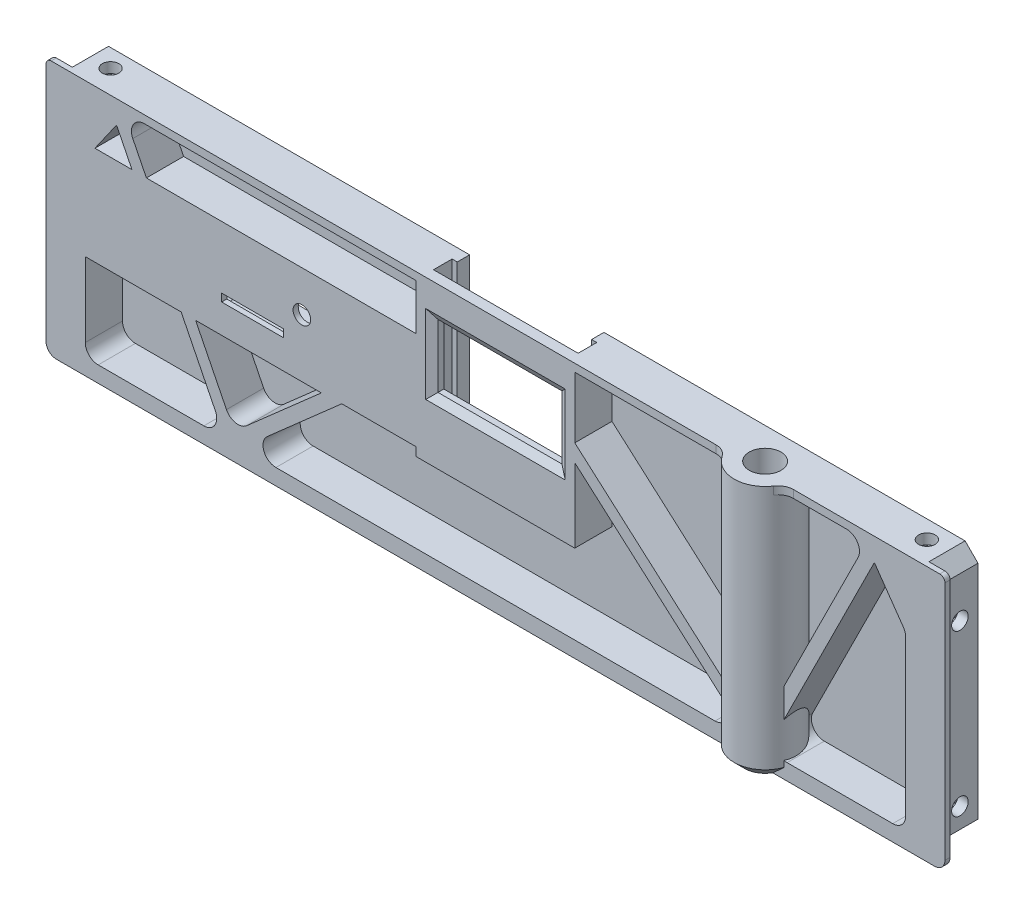
SolidWorks part; units mm, degrees
ref_plane "Front Plane" through (0, 0, 0) normal (0, 0, 1) x (1, 0, 0)
ref_plane "Top Plane" through (0, 0, 0) normal (0, 1, 0) x (1, 0, 0)
ref_plane "Right Plane" through (0, 0, 0) normal (1, 0, 0) x (0, 0, -1)
sketch "Sketch1" plane through (0, 0, 0) normal (0, 0, 1) x (1, 0, 0)
  line L1 (87, -25.55) -> (-87, -25.55)
  line L2 (87, -25.55) -> (87, 25.55)
  line L3 (87, 25.55) -> (-87, 25.55)
  line L4 (-87, -25.55) -> (-87, 25.55)
  line L5 (87, -25.55) -> (-87, 25.55) construction
  line L6 (87, 25.55) -> (-87, -25.55) construction
  point P0 (0, 0)
  dimension "D1" = 174
  dimension "D2" = 51.1
extrude "Boss-Extrude1" add sketch "Sketch1" against normal blind 8
sketch "Sketch2" plane through (0, 0, -8) normal (0, 0, -1) x (-1, 0, 0)
  line L5 (-87, -25.55) -> (-87, 25.55) construction
  line L6 (-87, 25.55) -> (87, 25.55) construction
  line L13 (85.4, -23.95) -> (85.4, 23.95)
  line L14 (-85.4, -23.95) -> (85.4, -23.95)
  line L15 (-85.4, 23.95) -> (-85.4, -23.95)
  line L16 (85.4, 23.95) -> (-85.4, 23.95)
  point P2 (0, 23.95)
  point P5 (85.4, 0)
  dimension "D1" = 1.6
  dimension "D2" = 1.6
extrude "Cut-Extrude1" cut sketch "Sketch2" against normal offset from surface (7 mm away) 1 flip side to cut up to face at (0, 0, 0)
chamfer "Chamfer1" distance 2.5 angle 45 4 edges at (-85.4, -23.95, -4.5) (-85.4, 23.95, -4.5) (85.4, -23.95, -4.5) (85.4, 23.95, -4.5)
fillet "Fillet1" radius 2 2 edges at (-87, -25.55, -0.5) (87, -25.55, -0.5)
sketch "Sketch3" plane through (0, 0, 0) normal (0, 0, 1) x (1, 0, 0)
  line L1 (-82.9, 23.95) -> (-85.4, 21.45) construction
  line L2 (-82.9, 23.95) -> (82.9, 23.95) construction
  line L3 (-82.9, 23.95) -> (-85.4, 21.45) construction
  line L4 (-82.9, 23.95) -> (82.9, 23.95) construction
  line L5 (85.4, 21.45) -> (82.9, 23.95) construction
  line L6 (85.4, 21.45) -> (85.4, -21.45) construction
  line L7 (82.9, -23.95) -> (85.4, -21.45) construction
  line L8 (82.9, -23.95) -> (-82.9, -23.95) construction
  line L9 (-85.4, -21.45) -> (-82.9, -23.95) construction
  line L10 (-85.4, -21.45) -> (-85.4, 21.45) construction
  line L11 (85.4, 21.45) -> (82.9, 23.95) construction
  line L12 (85.4, 21.45) -> (85.4, -21.45) construction
  line L13 (82.9, -23.95) -> (85.4, -21.45) construction
  line L14 (82.9, -23.95) -> (-82.9, -23.95) construction
  line L15 (-85.4, -21.45) -> (-82.9, -23.95) construction
  line L16 (-85.4, -21.45) -> (-85.4, 21.45) construction
  line L26 (79.4, -22.45) -> (-79.4, -22.45)
  line L27 (79.4, -22.45) -> (79.4, 22.45)
  line L28 (79.4, 22.45) -> (-79.4, 22.45)
  line L29 (-79.4, -22.45) -> (-79.4, 22.45)
  line L30 (79.4, -22.45) -> (-79.4, 22.45) construction
  line L31 (79.4, 22.45) -> (-79.4, -22.45) construction
  point P4 (0, 0)
  dimension "D1" = 3
  dimension "D2" = 6
extrude "Cut-Extrude2" cut sketch "Sketch3" against normal offset from surface (7.2 mm away) 0.8 up to face at (0, 0, -8)
sketch "Sketch9" plane through (0, 0, 0) normal (0, 0, 1) x (1, 0, 0)
  line L0 (-73.4, 22.45) -> (-73.4, 19.45)
  line L1 (-79.4, 22.45) -> (79.4, 22.45) construction
  line L2 (-73.4, 19.45) -> (-79.4, 10.8811)
  line L3 (-79.4, -22.45) -> (-79.4, 22.45) construction
  line L4 (-79.4, 10.8811) -> (-79.4, 22.45)
  line L5 (-79.4, 22.45) -> (-73.4, 22.45)
  dimension "D1" = 6
  dimension "D2" = 35
  dimension "D3" = 3
extrude "Boss-Extrude2" add sketch "Sketch9" against normal up to surface (7.2 mm away) up to face at (0, 0, -7.2)
hole_wizard "Ø3.0mm Dowel Hole1" positions "Sketch4" profile "Sketch5" hole size "Ø3.0" standard "ANSI Metric"
sketch "Sketch4" plane through (-85.4, 0, 0) normal (-1, 0, 0) x (0, 0, 1)
  line L0 (-4.5, 13.55) -> (-4.5, -17.55) construction
  line L2 (-8, -21.45) -> (-8, 21.45) construction
  line L4 (0, -25.55) -> (-1, -25.55) construction
  line L5 (-1, 25.55) -> (0, 25.55) construction
  point P0 (-4.5, 13.55)
  point P3 (-4.5, -17.55)
  dimension "D1" = 3.5
  dimension "D2" = 12
  dimension "D3" = 8
sketch "Sketch5" plane through (-85.4, 13.55, -4.5) normal (0, 1, 0) x (0, 0, 1)
  line L0 (0, 0) -> (0, 5)
  line L1 (0, 5) -> (1.6, 5)
  line L2 (1.6, 5) -> (1.6, 0)
  line L5 (1.6, 0) -> (0, 0)
  line L10 (0, 5) -> (-1.6, 5) construction
  line L11 (0, -6.35) -> (0, 107.95) construction
  dimension "Hole Dia." = 3.2
  dimension "Hole Depth" = 5
  dimension "Drill Angle" = 180
hole_wizard "Ø3.0mm Dowel Hole2" positions "Sketch7" profile "Sketch8" hole size "Ø3.0" standard "ANSI Metric"
sketch "Sketch7" plane through (0, 23.95, 0) normal (0, 1, 0) x (1, 0, 0)
  line L0 (-82.9, 8) -> (82.9, 8) construction
  line L2 (-87, 1) -> (-87, 0) construction
  point P0 (-79, 4.5)
  dimension "D1" = 3.5
  dimension "D2" = 8
sketch "Sketch8" plane through (-79, 23.95, -4.5) normal (1, 0, 0) x (0, 0, 1)
  line L0 (0, 0) -> (0, 5)
  line L1 (0, 5) -> (1.6, 5)
  line L2 (1.6, 5) -> (1.6, 0)
  line L5 (1.6, 0) -> (0, 0)
  line L10 (0, 5) -> (-1.6, 5) construction
  line L11 (0, -6.35) -> (0, 107.95) construction
  dimension "Hole Dia." = 3.2
  dimension "Hole Depth" = 5
  dimension "Drill Angle" = 180
sketch "Sketch10" plane through (-85.4, 0, 0) normal (-1, 0, 0) x (0, 0, 1)
  line L0 (-8, -21.45) -> (-8, 21.45) construction
  line L1 (-8, 16.3) -> (-1.75, 16.3)
  line L2 (-8, 16.3) -> (-8, 10.8)
  line L3 (-8, 10.8) -> (-1.75, 10.8)
  line L4 (-1.75, 16.3) -> (-1.75, 10.8)
  line L6 (-8, -14.8) -> (-1.75, -14.8)
  line L7 (-8, -14.8) -> (-8, -20.3)
  line L8 (-8, -20.3) -> (-1.75, -20.3)
  line L9 (-1.75, -14.8) -> (-1.75, -20.3)
  point P6 (-1.75, -17.55)
  point P8 (-1.75, 13.55)
  dimension "D1" = 5.5
  dimension "D2" = 2.75
extrude "Cut-Extrude3" cut sketch "Sketch10" against normal blind 1.8 from offset 2 offset against normal yes
sketch "Sketch11" plane through (0, 23.95, 0) normal (0, 1, 0) x (1, 0, 0)
  line L0 (-82.9, 8) -> (82.9, 8) construction
  line L1 (-81.75, 8) -> (-76.25, 8)
  line L2 (-81.75, 8) -> (-81.75, 1.75)
  line L3 (-81.75, 1.75) -> (-76.25, 1.75)
  line L4 (-76.25, 8) -> (-76.25, 1.75)
  point P6 (-79, 1.75)
  dimension "D1" = 5.5
  dimension "D2" = 2.75
extrude "Cut-Extrude4" cut sketch "Sketch11" against normal blind 1.8 from offset 2 offset against normal yes
mirror "Mirror1" about plane through (0, 0, 0) normal (1, 0, 0) of "Cut-Extrude4", "Cut-Extrude3", "Ø3.0mm Dowel Hole2", "Ø3.0mm Dowel Hole1", "Boss-Extrude2"
sketch "Sketch12" plane through (0, 0, -7.2) normal (0, 0, 1) x (1, 0, 0)
  line L0 (-73.4, 22.45) -> (-51.0137, -22.45) construction
  line L1 (-79.4, -22.45) -> (79.4, -22.45) construction
  line L2 (-51.0137, -22.45) -> (0, 22.45) construction
  line L3 (73.4, 22.45) -> (-73.4, 22.45) construction
  line L4 (0, 22.45) -> (51.0137, -22.45) construction
  line L5 (51.0137, -22.45) -> (73.4, 22.45) construction
  line L6 (-74.5187, 21.8923) -> (-51.9874, -23.2985)
  line L7 (-50.4317, -23.603) -> (0, 20.7848)
  line L8 (0, 20.7848) -> (50.4317, -23.603)
  line L9 (51.9874, -23.2985) -> (74.5187, 21.8923)
  line L10 (-72.2813, 23.0077) -> (-50.62, -20.4382)
  line L11 (-50.62, -20.4382) -> (-0.6607, 23.5337)
  line L12 (0.6607, 23.5337) -> (50.62, -20.4382)
  line L13 (50.62, -20.4382) -> (72.2813, 23.0077)
  line L14 (0, 20.7848) -> (51.4074, -24.4618) construction
  line L15 (51.4074, -24.4618) -> (74.5187, 21.8923) construction
  line L16 (-50.62, -20.4382) -> (0, 24.1152) construction
  line L17 (0, 24.1152) -> (50.62, -20.4382) construction
  line L18 (-74.5187, 21.8923) -> (-51.4074, -24.4618) construction
  line L19 (-51.4074, -24.4618) -> (0, 20.7848) construction
  line L20 (79.4, -22.45) -> (-79.4, -22.45) construction
  line L21 (-79.4, -22.45) -> (-79.4, 10.8811) construction
  arc A0 (-74.5187, 21.8923) -> (-72.2813, 23.0077) centre (-73.4, 22.45) cw
  arc A1 (74.5187, 21.8923) -> (72.2813, 23.0077) centre (73.4, 22.45) ccw
  arc A2 (50.4317, -23.603) -> (51.9874, -23.2985) centre (51.0924, -22.8524) ccw
  arc A3 (-0.6607, 23.5337) -> (0.6607, 23.5337) centre (0, 22.783) cw
  arc A4 (-51.9874, -23.2985) -> (-50.4317, -23.603) centre (-51.0924, -22.8524) ccw
  dimension "D3" = 1
  dimension "D1" = 1.25
  dimension "D2" = 26.5
extrude "Boss-Extrude3" add sketch "Sketch12" along normal up to surface (7.2 mm away) up to face at (0, 7.5828, 0)
sketch "Sketch13" plane through (0, 0, 0) normal (0, 0, 1) x (1, 0, 0)
  line L0 (-73.4, 19.45) -> (-73.4, 19.6486)
  line L1 (-73.4, 19.6486) -> (-73.301, 19.45)
  line L2 (-73.4, 19.6486) -> (-52.4104, -22.45) construction
  line L3 (-73.301, 19.45) -> (-73.4, 19.45)
  line L4 (0, 0) -> (0, 25.4565) construction
  line L5 (73.301, 19.45) -> (73.4, 19.45)
  line L6 (73.4, 19.6486) -> (73.301, 19.45)
  line L7 (73.4, 19.45) -> (73.4, 19.6486)
  dimension "D1" = 0.1986
extrude "Small Fix" add sketch "Sketch13" against normal up to surface (7.2 mm away) up to face at (-71.6021, 1.0159, -7.2)
fillet "Fillet2" radius 2.5 15 edges at (79.4, -22.45, -3.6) (79.4, 10.8811, -3.6) (52.4104, -22.45, -3.6) (72.0032, 22.45, -3.6) (50.62, -20.4382, -3.6) (1.892, 22.45, -3.6) (49.1217, -22.45, -3.6) (0, 20.7848, -3.6) (-49.1217, -22.45, -3.6) (-1.892, 22.45, -3.6) (-50.62, -20.4382, -3.6) (-72.0032, 22.45, -3.6) (-79.4, 10.8811, -3.6) (-79.4, -22.45, -3.6) (-52.4104, -22.45, -3.6)
fillet "Fillet3" radius 0.1 4 edges at (73.4, 19.45, -3.6) (73.301, 19.45, -3.6) (-73.301, 19.45, -3.6) (-73.4, 19.45, -3.6)
sketch "Sketch14" plane through (0, 0, -8) normal (0, 0, -1) x (-1, 0, 0)
  line L1 (-13.85, 22.45) -> (13.85, 22.45) construction
  line L2 (-13.85, 22.45) -> (-13.85, -5.55) construction
  line L3 (-13.85, -5.55) -> (13.85, -5.55) construction
  line L4 (13.85, 22.45) -> (13.85, -5.55) construction
  line L5 (82.9, 23.95) -> (-82.9, 23.95) construction
  line L6 (-15.35, 23.95) -> (-15.35, -7.05)
  line L7 (-15.35, -7.05) -> (15.35, -7.05)
  line L8 (15.35, 23.95) -> (15.35, -7.05)
  line L9 (-15.35, 22.45) -> (-15.35, -7.05) construction
  line L10 (15.35, 22.45) -> (15.35, -7.05) construction
  line L11 (-15.35, 23.95) -> (15.35, 23.95)
  point P6 (0, -5.55)
  dimension "D1" = 28
  dimension "D2" = 27.7
  dimension "D3" = 1.5
  dimension "D4" = 1.5
extrude "Boss-Extrude4" add sketch "Sketch14" against normal up to surface (8 mm away) up to face at (-42.2461, 7.7039, 0)
sketch "Sketch17" plane through (0, 23.95, 0) normal (0, 1, 0) x (1, 0, 0)
  line L0 (87, 0) -> (-87, 0) construction
  line L1 (-14, 5.6) -> (14, 5.6)
  line L2 (-14, 5.6) -> (-14, 2)
  line L3 (-14, 2) -> (14, 2)
  line L4 (14, 5.6) -> (14, 2)
  point P8 (0, 2)
  point P11 (-13.85, 8)
  dimension "D1" = 3.6
  dimension "D2" = 2
  dimension "D3" = 0.15
extrude "Cut-Extrude6" cut sketch "Sketch17" against normal up to vertex (29.5 mm away) up to point (13.85, -5.55, -8)
sketch "Sketch18" plane through (0, 0, -8) normal (0, 0, -1) x (-1, 0, 0)
  line L0 (82.9, 23.95) -> (-82.9, 23.95) construction
  line L1 (-13, 23.95) -> (13, 23.95)
  line L2 (-13, 23.95) -> (-13, -2.55)
  line L3 (-13, -2.55) -> (13, -2.55)
  line L4 (13, 23.95) -> (13, -2.55)
  line L5 (-14, -5.55) -> (14, -5.55) construction
  point P6 (0, -2.55)
  dimension "D1" = 26
  dimension "D2" = 3
extrude "Cut-Extrude7" cut sketch "Sketch18" against normal up to surface (6 mm away) up to face at (0, 9.2, -2)
sketch "Sketch19" plane through (0, 0, 0) normal (0, 0, 1) x (1, 0, 0)
  line L1 (-13, 18.2) -> (13, 18.2) construction
  line L2 (-13, 18.2) -> (-13, 3.95) construction
  line L3 (-13, 3.95) -> (13, 3.95) construction
  line L4 (13, 18.2) -> (13, 3.95) construction
  line L6 (-12, 17.2) -> (12, 17.2)
  line L7 (12, 17.2) -> (12, 4.95)
  line L8 (-12, 4.95) -> (12, 4.95)
  line L9 (-12, 17.2) -> (-12, 4.95)
  dimension "D1" = 1
extrude "Cut-Extrude8" cut sketch "Sketch19" against normal up to surface (2 mm away) up to face at (0, 9.2, -2)
chamfer "Chamfer2" distance 1.5 angle 30 4 edges at (0, 4.95, 0) (-12, 11.075, 0) (12, 11.075, 0) (0, 17.2, 0) first distance on face at (0, 11.075, 0)
sketch "Sketch21" plane through (0, 0, -1) normal (0, 0, -1) x (-1, 0, 0)
  line L0 (87, -23.55) -> (87, 25.55) construction
  line L1 (-87, 25.55) -> (87, 25.55)
  line L2 (-87, 25.55) -> (-87, 23.95)
  line L3 (-87, 23.95) -> (87, 23.95)
  line L4 (87, 25.55) -> (87, 23.95)
  line L5 (82.9, 23.95) -> (-82.9, 23.95) construction
extrude "Cut-Extrude10" cut sketch "Sketch21" against normal through all
sketch "Sketch22" plane through (0, 0, 0) normal (0, 0, 1) x (1, 0, 0)
  line L0 (-79.4, -5.55) -> (-33.7045, -5.55)
  line L1 (-79.4, -5.55) -> (-79.4, 13.55)
  line L2 (-79.4, 13.55) -> (-23.6, 13.55)
  line L3 (-23.6, 3.3435) -> (-23.6, 13.55) construction
  line L4 (-81.6, 0.95) -> (-25.6, 0.95) construction
  line L5 (-81.6, 0.95) -> (-81.6, 2.55) construction
  line L6 (-81.6, 2.55) -> (-25.6, 2.55) construction
  line L7 (-25.6, 0.95) -> (-25.6, 2.55) construction
  line L9 (-33.7045, -5.55) -> (-15.35, 10.6048)
  line L10 (-15.35, 13.55) -> (-23.6, 13.55)
  line L12 (-15.35, 10.6048) -> (-48.1808, -18.2914) construction
  line L14 (-79.4, 10.0929) -> (-79.4, -19.95) construction
  line L15 (82.9, -23.95) -> (-82.9, -23.95) construction
  line L16 (-87, 23.95) -> (-87, -23.55) construction
  line L17 (-15.35, 10.6048) -> (-15.35, 13.55)
  line L18 (-15.35, 22.45) -> (-15.35, 10.6048) construction
  line L19 (-15.35, 10.6048) -> (-48.1808, -18.2914) construction
  dimension "D1" = 11
  dimension "D2" = 2
  dimension "D3" = 56
  dimension "D4" = 1.6
  dimension "D5" = 24.9
  dimension "D6" = 5.4
  dimension "D7" = 6.5
extrude "Boss-Extrude5" add sketch "Sketch22" against normal up to surface (7.2 mm away) up to face at (-71.6654, -0.5445, -7.2)
sketch "Sketch23" plane through (0, 0, -8) normal (0, 0, -1) x (-1, 0, 0)
  line L1 (24.1, 12.55) -> (83.1, 12.55)
  line L2 (24.1, 12.55) -> (24.1, 0.95)
  line L3 (24.1, 0.95) -> (83.1, 0.95)
  line L4 (83.1, 12.55) -> (83.1, 0.95)
  line L5 (81.6, 0.95) -> (25.6, 0.95) construction
  line L6 (81.6, 0.95) -> (81.6, 2.55) construction
  line L7 (79.4, 13.55) -> (23.6, 13.55) construction
  point P6 (53.6, 0.95)
  point P7 (53.6, 0.95)
  dimension "D1" = 1.5
  dimension "D2" = 1
extrude "Cut-Extrude11" cut sketch "Sketch23" along direction (0, 0, 1) on the side against the normal blind 7
sketch "Sketch25" plane through (0, 0, -8) normal (0, 0, -1) x (-1, 0, 0)
  line L0 (24.1, 0.95) -> (83.1, 0.95) construction
  line L1 (32.1, 0.95) -> (67.1, 0.95)
  line L2 (32.1, 0.95) -> (32.1, -1.05)
  line L3 (32.1, -1.05) -> (67.1, -1.05)
  line L4 (67.1, 0.95) -> (67.1, -1.05)
  line L5 (24.1, 12.55) -> (24.1, 0.95) construction
  line L6 (83.1, 12.55) -> (83.1, 0.95) construction
  dimension "D1" = 8
  dimension "D2" = 16
  dimension "D3" = 2
extrude "Cut-Extrude12" cut sketch "Sketch25" against normal up to surface (7 mm away) up to face at (-53.6, 6.75, -1)
sketch "Sketch26" plane through (0, 0, -8) normal (0, 0, -1) x (-1, 0, 0)
  line L0 (32.1, 0.95) -> (24.1, 0.95) construction
  line L1 (24.1, 12.55) -> (29.1, 12.55)
  line L2 (24.1, 12.55) -> (24.1, 3.15)
  line L3 (24.1, 3.15) -> (29.1, 3.15)
  line L4 (29.1, 12.55) -> (29.1, 3.15)
  line L5 (83.1, 12.55) -> (76.1, 12.55)
  line L6 (83.1, 12.55) -> (83.1, 3.15)
  line L7 (83.1, 3.15) -> (76.1, 3.15)
  line L8 (76.1, 12.55) -> (76.1, 3.15)
  dimension "D1" = 5
  dimension "D2" = 7
  dimension "D3" = 2.2
extrude "Boss-Extrude6" add sketch "Sketch26" against normal up to surface (7 mm away) up to face at (-51.6, 3.35, -1)
sketch "Sketch27" plane through (0, 0, 0) normal (0, 0, 1) x (1, 0, 0)
  line L1 (-52.511, 0.535) -> (-41.511, 0.535) construction
  line L2 (-52.511, 0.535) -> (-52.511, 0.035) construction
  line L3 (-52.511, 0.035) -> (-41.511, 0.035) construction
  line L4 (-41.511, 0.535) -> (-41.511, 0.035) construction
  line L5 (-24.1, 3.15) -> (-24.1, 0.95) construction
  line L8 (-57.7737, 0.535) -> (-47.7737, 0.535) construction
  line L10 (-53.011, 1.035) -> (-41.011, 1.035)
  line L11 (-41.011, 1.035) -> (-41.011, -0.465)
  line L12 (-53.011, -0.465) -> (-41.011, -0.465)
  line L13 (-53.011, 1.035) -> (-53.011, -0.465)
  circle A0 centre (-37.475, 5.65) radius 1.2 construction
  arc A1 (-38.5, 6.1) -> (-38.5, 3.7) centre (-38.5, 4.9) ccw construction
  circle A2 centre (-37.475, 5.65) radius 1.7
  point P4 (-41.511, 0.285)
  dimension "D1" = 0.5
  dimension "D2" = 0.5
  dimension "D3" = 11
  dimension "D4" = 17.411
  dimension "D5" = 4.615
  dimension "D6" = 4.036
  dimension "D7" = 0.5
extrude "Cut-Extrude13" cut sketch "Sketch27" against normal up to surface (1 mm away) up to face at (-51.9333, 3.2833, -1)
fillet "Fillet4" radius 1 2 edges at (87, 23.95, -0.5) (-87, 23.95, -0.5)
sketch "Sketch29" plane through (0, 23.95, 0) normal (0, 1, 0) x (1, 0, 0)
  line L0 (50.195, 8) -> (50.195, 0) construction
  line L1 (13, 8) -> (82.9, 8) construction
  line L2 (86, 0) -> (-86, 0) construction
  circle A0 centre (50.195, 2) radius 3 construction
  circle A1 centre (50.195, 2) radius 6
  dimension "D1" = 6
  dimension "D2" = 12
extrude "Boss-Extrude8" add sketch "Sketch29" against normal up to surface (49.5 mm away) up to face at (0, -25.55, -0.5)
sketch "Sketch30" plane through (0, 23.95, 0) normal (0, 1, 0) x (1, 0, 0)
  circle A0 centre (50.195, 2) radius 3 construction
  circle A1 centre (50.195, 2) radius 3 construction
  circle A2 centre (50.195, 2) radius 3.075
  dimension "D1" = 6.15
extrude "Cut-Extrude14" cut sketch "Sketch30" against normal offset from surface (43.9 mm away) 4 up to face at (-18.2377, -23.95, -4.8432)
sketch "Sketch31" plane through (0, -23.95, 0) normal (0, -1, 0) x (1, 0, 0)
  line L0 (44.2789, -1) -> (-82.9, -1) construction
  line L1 (44.195, -1) -> (56.195, -1)
  line L2 (44.195, -1) -> (44.195, -8)
  line L3 (44.195, -8) -> (56.195, -8)
  line L4 (56.195, -1) -> (56.195, -8)
  line L5 (82.9, -8) -> (50.195, -8) construction
  circle A0 centre (50.195, -2) radius 6 construction
extrude "Cut-Extrude15" cut sketch "Sketch31" along normal up to surface (1.6 mm away) up to face at (25.0975, -25.55, -0.875)
chamfer "Chamfer3" distance 2 angle 45 1 edges at (50.195, -25.55, 4)
fillet "Fillet5" radius 3 2 edges at (55.8519, 23.2, 0) (44.5381, 23.2, 0)
sketch "Sketch32" plane through (0, 0, -1.75) normal (0, 0, -1) x (-1, 0, 0)
  line L1 (-81.75, 21.95) -> (-76.25, 21.95)
  line L2 (-81.75, 21.95) -> (-81.75, 20.15)
  line L3 (-81.75, 20.15) -> (-76.25, 20.15)
  line L4 (-76.25, 21.95) -> (-76.25, 20.15)
  line L5 (-83.4, 16.3) -> (-81.6, 16.3)
  line L6 (-83.4, 16.3) -> (-83.4, 10.8)
  line L7 (-83.4, 10.8) -> (-81.6, 10.8)
  line L8 (-81.6, 16.3) -> (-81.6, 10.8)
  line L9 (-83.4, -14.8) -> (-81.6, -14.8)
  line L10 (-83.4, -14.8) -> (-83.4, -20.3)
  line L11 (-83.4, -20.3) -> (-81.6, -20.3)
  line L12 (-81.6, -14.8) -> (-81.6, -20.3)
  line L13 (76.25, 21.95) -> (81.75, 21.95)
  line L14 (76.25, 21.95) -> (76.25, 20.15)
  line L15 (76.25, 20.15) -> (81.75, 20.15)
  line L16 (81.75, 21.95) -> (81.75, 20.15)
  line L17 (81.6, 16.3) -> (83.4, 16.3)
  line L18 (81.6, 16.3) -> (81.6, 10.8)
  line L19 (81.6, 10.8) -> (83.4, 10.8)
  line L20 (83.4, 16.3) -> (83.4, 10.8)
  line L21 (81.6, -14.8) -> (83.4, -14.8)
  line L22 (81.6, -14.8) -> (81.6, -20.3)
  line L23 (81.6, -20.3) -> (83.4, -20.3)
  line L24 (83.4, -14.8) -> (83.4, -20.3)
extrude "Cut-Extrude17" cut sketch "Sketch32" against normal blind 0.1
sketch "Sketch35" plane through (0, 0, 0) normal (0, 0, 1) x (1, 0, 0)
  line L0 (-29.7496, -5.3995) -> (-15.35, -5.3995)
  line L1 (-44.1492, -18.0734) -> (-15.35, 7.2744) construction
  line L2 (-15.35, -7.05) -> (-15.35, 7.2744) construction
  line L3 (-15.35, -5.3995) -> (-15.35, 7.2744)
  line L4 (-15.35, 7.2744) -> (-29.7496, -5.3995)
extrude "Boss-Extrude9" add sketch "Sketch35" against normal up to surface (7.2 mm away) up to face at (0, -10.2175, -7.2)
sketch "Sketch34" plane through (0, 0, -8) normal (0, 0, -1) x (-1, 0, 0)
  line L0 (67.1, 0.95) -> (83.1, 0.95) construction
  line L1 (53.411, 0.95) -> (76.611, 0.95)
  line L2 (53.411, 0.95) -> (53.411, -4.15)
  line L3 (53.411, -4.15) -> (76.611, -4.15)
  line L4 (76.611, 0.95) -> (76.611, -4.15)
  line L6 (76.1, 12.55) -> (29.1, 12.55) construction
  line L7 (76.1, 3.15) -> (76.1, 12.55) construction
  line L8 (34.225, -2.45) -> (23.975, -2.45)
  line L9 (34.225, -2.45) -> (34.225, 12.55)
  line L10 (34.225, 12.55) -> (23.975, 12.55)
  line L11 (23.975, -2.45) -> (23.975, 12.55)
  circle A0 centre (37.475, 5.65) radius 1.7 construction
  dimension "D5" = 3.25
  dimension "D1" = 23.2
  dimension "D2" = 5.1
  dimension "D3" = 0.511
  dimension "D4" = 10.25
  dimension "D6" = 15
extrude "Cut-Extrude18" cut sketch "Sketch34" against normal up to surface (7 mm away) up to face at (-47.011, 0.285, -1)
extrude "Cut-Extrude19" cut sketch "Sketch10<2>" along direction (-1, 0, 0) on the side against the normal up to surface (3.8 mm away) from surface contours L2 L3 L4 L1 up to face at (-81.6, 13.375, -3.975) starting at face at (-83.4, 13.55, -4.825)
sketch "Sketch10<2>" plane through (-85.4, 0, 0) normal (-1, 0, 0) x (0, 0, 1) same geometry as "Sketch10"
sketch "Sketch36" plane through (-85.4, 0, 0) normal (-1, 0, 0) x (0, 0, 1)
  circle A0 centre (-4.5, 13.55) radius 1.6
  circle A1 centre (-4.5, 13.55) radius 1.6 construction
extrude "Cut-Extrude20" cut sketch "Sketch36" against normal up to surface (5 mm away) up to face at (-80.4, 13.85, -4.5)
sketch "Sketch37" plane through (0, 0, 0) normal (0, 0, 1) x (1, 0, 0)
  line L0 (-41.011, -0.465) -> (-41.011, 1.035) construction
  line L1 (-53.011, 1.535) -> (-41.011, 1.535)
  line L2 (-53.011, 1.535) -> (-53.011, -0.465)
  line L3 (-53.011, -0.465) -> (-41.011, -0.465)
  line L4 (-41.011, 1.535) -> (-41.011, -0.465)
  line L6 (-53.011, -0.465) -> (-41.011, -0.465)
  line L7 (-53.011, -0.465) -> (-53.011, 0.035)
  line L8 (-53.011, 0.035) -> (-41.011, 0.035)
  line L9 (-41.011, -0.465) -> (-41.011, 0.035)
  dimension "D1" = 1.5
  dimension "D2" = 0.5
extrude "Boss-Extrude10" add sketch "Sketch37" against normal up to surface (1 mm away) contours L8 L2 L3 L4 region at (-47.011, -0.215, 0) up to face at (-57.9037, 1.5, -1)
extrude "Cut-Extrude21" cut sketch "Sketch37<3>" against normal blind 10 contours L2 L8 L4 L1 region at (-47.011, 0.785, 0)
sketch "Sketch37<3>" plane through (0, 0, 0) normal (0, 0, 1) x (1, 0, 0) same geometry as "Sketch37"
